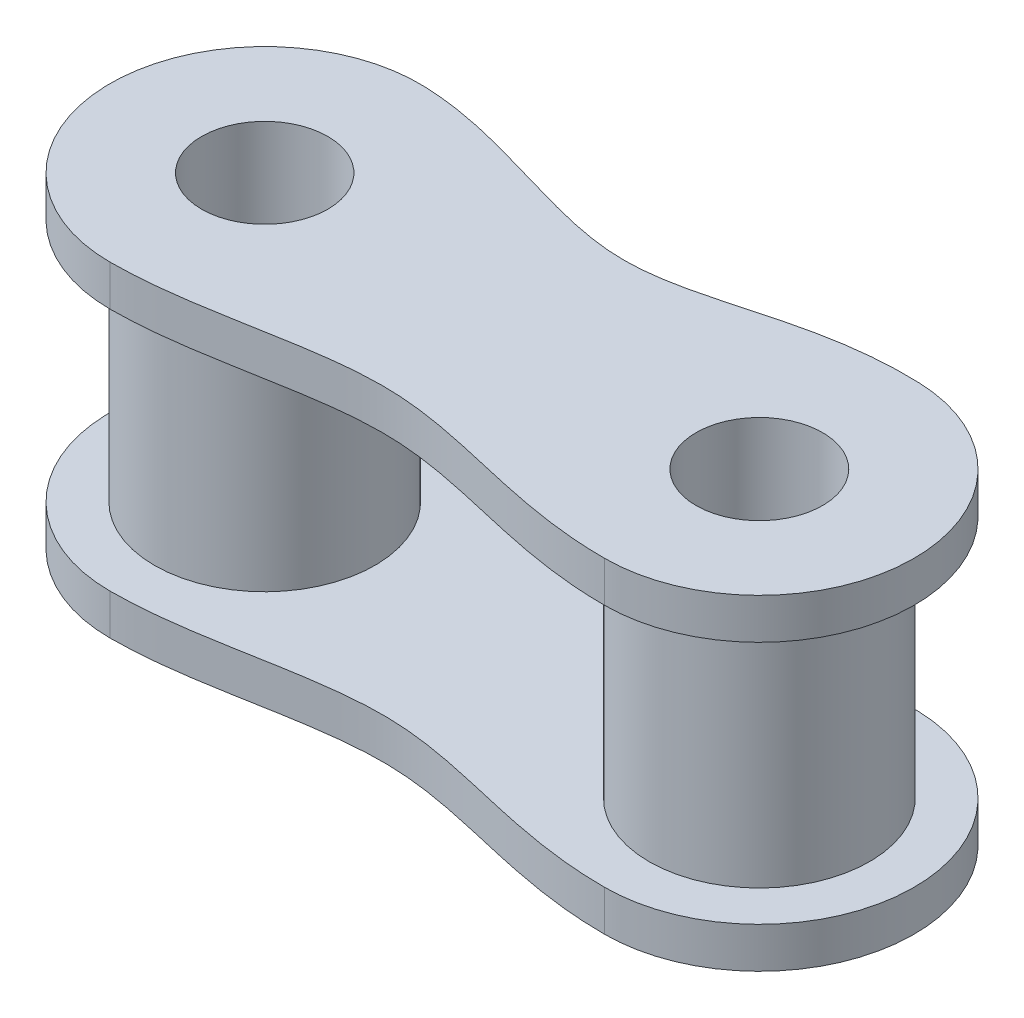
SolidWorks part; units mm, degrees
material "铸造合金钢"
ref_plane "前视基准面" through (0, 0, 0) normal (0, 0, 1) x (1, 0, 0)
ref_plane "上视基准面" through (0, 0, 0) normal (0, 1, 0) x (1, 0, 0)
ref_plane "右视基准面" through (0, 0, 0) normal (1, 0, 0) x (0, 0, -1)
sketch "草图1" plane through (0, 0, 0) normal (0, 1, 0) x (1, 0, 0)
  circle A0 centre (-56.2357, 24.7329) radius 3.8
  circle A1 centre (-43.8557, 24.5057) radius 3.8
  circle A7 centre (-56.2357, 24.7329) radius 1.55
  circle A8 centre (-43.8557, 24.5057) radius 1.5539
  spline S0 degree 3 poles (-56.0931, 28.5302) (-53.9426, 28.4494) (-49.7686, 26.1495) (-46.434, 28.3981) (-43.723, 28.3034) knots 0 0 0 0 0.490575 1 1 1 1
  spline S1 degree 3 poles (-56.2357, 20.9329) (-54.1058, 20.9329) (-49.896, 22.4778) (-46.2524, 20.7057) (-43.8557, 20.7057) knots 0 0 0 0 0.49851 1 1 1 1
sketch "草图3" plane through (0, 0, 0) normal (0, 1, 0) x (1, 0, 0)
  circle A0 centre (-56.2357, 24.7329) radius 2.7083
  circle A1 centre (-43.8557, 24.5057) radius 2.7083
  dimension "D1" = 5.4166
extrude "凸台-拉伸8" add sketch "草图3" along normal blind 3 and the other way blind 3 contours A0 | A1 region at (-56.2357, 0, -24.7329)
sketch "草图4" plane through (0, 0, 0) normal (0, 1, 0) x (1, 0, 0)
  circle A0 centre (-56.2357, 24.7329) radius 1.55
  circle A1 centre (-43.8557, 24.5057) radius 1.5539
extrude "切除-拉伸1" cut sketch "草图4" against normal blind 6 and the other way blind 3
sketch "草图7" plane through (0, -3, 0) normal (0, -1, 0) x (1, 0, 0)
  circle A1 centre (-43.8557, -24.5057) radius 1.5539
  circle A2 centre (-43.8557, -24.5057) radius 1.5539
  circle A3 centre (-56.2357, -24.7329) radius 1.55
  circle A4 centre (-56.2357, -24.7329) radius 1.55
  circle A5 centre (-43.8557, -24.5057) radius 3.8
  circle A6 centre (-43.8557, -24.5057) radius 3.8
  circle A7 centre (-56.2357, -24.7329) radius 3.8
  circle A8 centre (-56.2357, -24.7329) radius 3.8
  spline S0 degree 3 poles (-38.5058, 2970.5982) (-121.075, -178.4888) (-24.6821, 115.8306) (-34.009, -162.7507) (1461.0641, 2565.8142) knots -5.25994 -5.25994 -5.25994 -5.25994 0.490575 5.962914 5.962914 5.962914 5.962914 only from (-56.0931, -28.5302) to (-43.723, -28.3034) construction
  spline S1 degree 3 poles (38.0208, -3018.5861) (-123.8084, 113.6518) (-29.2173, -151.338) (-23.2118, 102.6478) (1232.8358, -2734.4178) knots -5.921037 -5.921037 -5.921037 -5.921037 0.49851 6.587332 6.587332 6.587332 6.587332 only from (-56.2357, -20.9329) to (-43.8557, -20.7057) construction
  spline S2 degree 3 poles (-56.0931, -28.5302) (-53.9426, -28.4494) (-49.7686, -26.1495) (-46.434, -28.3981) (-43.723, -28.3034) knots 0 0 0 0 0.490575 1 1 1 1
  spline S3 degree 3 poles (-56.2357, -20.9329) (-54.1058, -20.9329) (-49.896, -22.4778) (-46.2524, -20.7057) (-43.8557, -20.7057) knots 0 0 0 0 0.49851 1 1 1 1
  circle M5 centre (-56.2357, -24.7329) radius 1.55
  circle M6 centre (-56.2357, -24.7329) radius 2.7083
  dimension "D1" = 0
  dimension "D2" = 0
  dimension "D3" = 0
  dimension "D4" = 0
extrude "凸台-拉伸9" add sketch "草图7" along normal blind 1 contours A8 M6 | S3 A8 S2 A6 | A6 A2 | M6 M5 region at (-59.9276, -3, -24.8022) region at (-46.9063, -3, -24.4949) region at (-58.8674, -3, -24.7329)
sketch "草图16" plane through (0, 3, 0) normal (0, 1, 0) x (1, 0, 0)
  circle A1 centre (-56.2357, 24.7329) radius 1.55
  circle A2 centre (-56.2357, 24.7329) radius 1.55
  circle A3 centre (-43.8557, 24.5057) radius 1.5539
  circle A4 centre (-43.8557, 24.5057) radius 1.5539
  dimension "D1" = 0
  dimension "D2" = 0
sketch "草图17" plane through (0, 3, 0) normal (0, 1, 0) x (1, 0, 0)
  circle A1 centre (-56.2357, 24.7329) radius 1.55
  circle A2 centre (-56.2357, 24.7329) radius 1.55
  circle A3 centre (-43.8557, 24.5057) radius 1.5539
  circle A4 centre (-43.8557, 24.5057) radius 1.5539
  dimension "D1" = 0
  dimension "D2" = 0
sketch "草图18" plane through (0, 3, 0) normal (0, 1, 0) x (1, 0, 0)
  circle A1 centre (-56.2357, 24.7329) radius 1.55
  circle A2 centre (-56.2357, 24.7329) radius 1.55
  circle A3 centre (-43.8557, 24.5057) radius 1.5539
  circle A4 centre (-43.8557, 24.5057) radius 1.5539
  arc A6 (-56.0931, 28.5302) -> (-56.2357, 20.9329) centre (-56.2357, 24.7329) ccw
  arc A7 (-43.8557, 20.7057) -> (-43.723, 28.3034) centre (-43.8557, 24.5057) ccw
  arc A8 (-56.0931, 28.5302) -> (-56.2357, 20.9329) centre (-56.2357, 24.7329) ccw
  arc A9 (-43.8557, 20.7057) -> (-43.723, 28.3034) centre (-43.8557, 24.5057) ccw
  spline S2 degree 3 poles (90.8168, 4017.1206) (-133.3718, -141.1039) (-24.827, 177.651) (-22.8416, -127.8689) (1636.1986, 3649.391) knots -6.539049 -6.539049 -6.539049 -6.539049 0.49851 7.179718 7.179718 7.179718 7.179718 only from (-56.2357, 20.9329) to (-43.8557, 20.7057)
  spline S3 degree 3 poles (1939.9909, -3443.6747) (-35.1282, 190.3926) (-19.4181, -144.7679) (-130.7982, 208.7801) (-10.9856, -3970.0961) knots -5.493872 -5.493872 -5.493872 -5.493872 0.509425 6.811121 6.811121 6.811121 6.811121 only from (-43.723, 28.3034) to (-56.0931, 28.5302)
  spline S4 degree 3 poles (-56.2357, 20.9329) (-54.1058, 20.9329) (-49.896, 22.4778) (-46.2524, 20.7057) (-43.8557, 20.7057) knots 0 0 0 0 0.49851 1 1 1 1
  spline S5 degree 3 poles (-43.723, 28.3034) (-46.434, 28.3981) (-49.7686, 26.1495) (-53.9426, 28.4494) (-56.0931, 28.5302) knots 0 0 0 0 0.509425 1 1 1 1
  dimension "D1" = 0
  dimension "D2" = 0
  dimension "D3" = 0
extrude "凸台-拉伸17" add sketch "草图18" along normal blind 1
